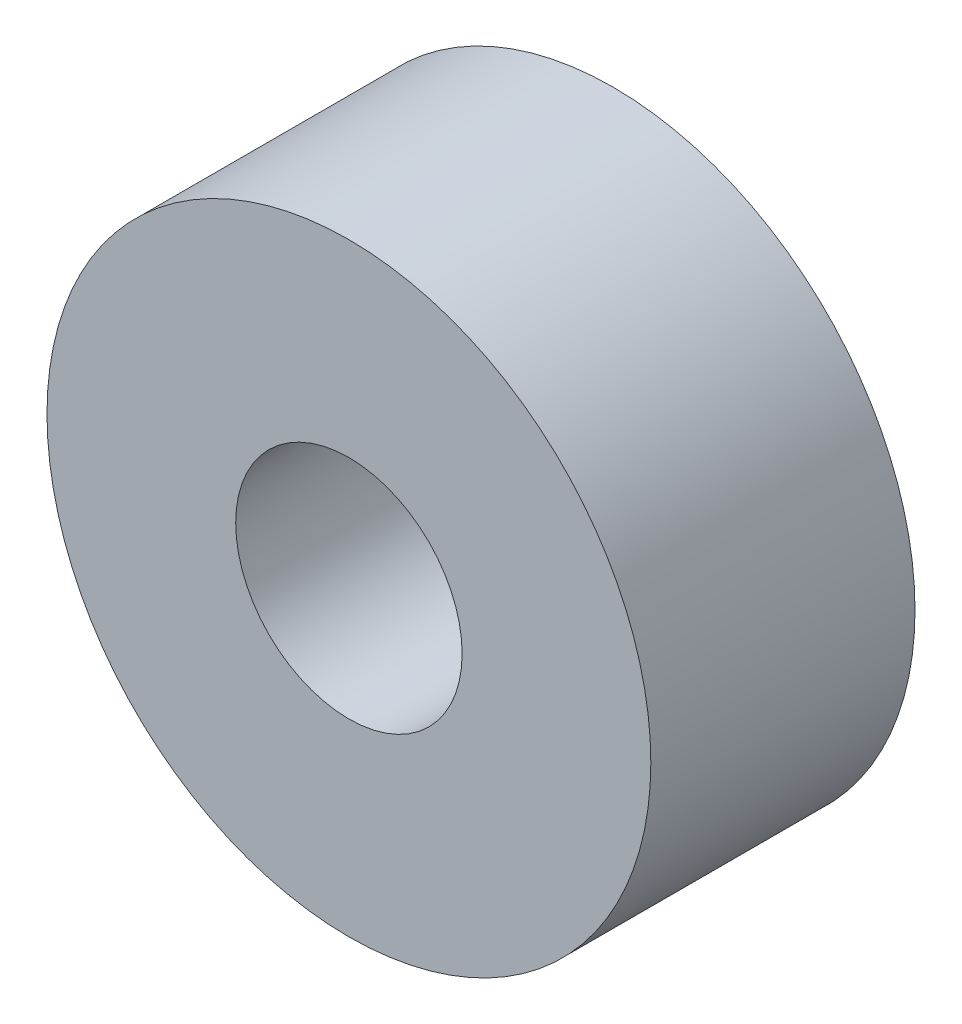
SolidWorks part; units mm, degrees
ref_plane "前视基准面" through (0, 0, 0) normal (0, 0, 1) x (1, 0, 0)
ref_plane "上视基准面" through (0, 0, 0) normal (0, 1, 0) x (1, 0, 0)
ref_plane "右视基准面" through (0, 0, 0) normal (1, 0, 0) x (0, 0, -1)
other "Configuration Table"
sketch "草图1" plane through (0, 0, 0) normal (0, 0, 1) x (1, 0, 0)
  circle A0 centre (0, 0) radius 4
  circle A1 centre (0, 0) radius 1.5
  dimension "D1" = 3
  dimension "D2" = 8
extrude "凸台-拉伸1" add sketch "草图1" along normal blind 3.5
